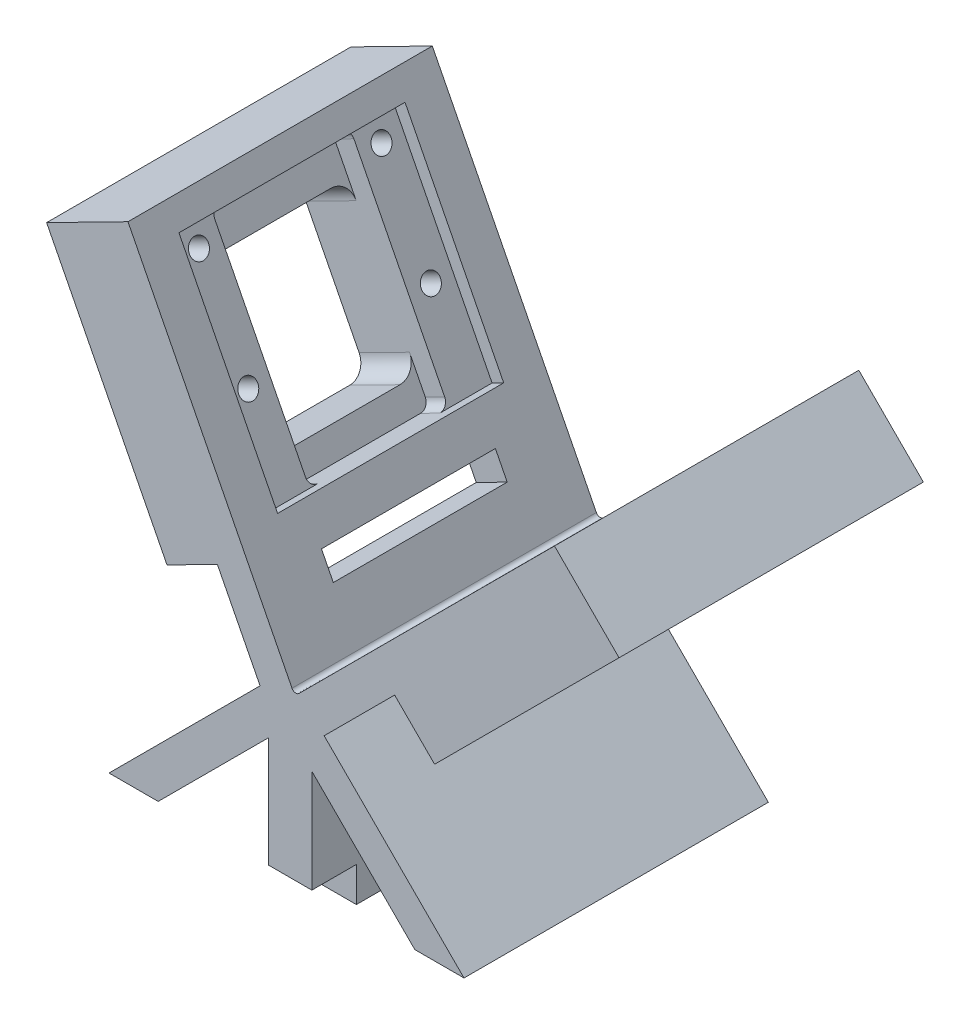
SolidWorks part; units mm, degrees
ref_plane "Front Plane" through (0, 0, 0) normal (0, 0, 1) x (1, 0, 0)
ref_plane "Top Plane" through (0, 0, 0) normal (0, 1, 0) x (1, 0, 0)
ref_plane "Right Plane" through (0, 0, 0) normal (1, 0, 0) x (0, 0, -1)
sketch "Sketch1" plane through (0, 0, 0) normal (0, 0, 1) x (1, 0, 0)
  line L0 (6.55, 4.55) -> (-6.55, 4.55)
  line L1 (4.05, 2.05) -> (-4.05, 2.05)
  line L2 (4.05, 2.05) -> (4.05, -2.05)
  line L3 (4.05, -2.05) -> (2.05, -2.05)
  line L4 (-4.05, 2.05) -> (-4.05, -2.05)
  line L5 (4.05, 2.05) -> (-4.05, -2.05) construction
  line L6 (4.05, -2.05) -> (-4.05, 2.05) construction
  line L7 (-6.55, 4.55) -> (-6.55, -4.55)
  line L8 (6.55, -4.55) -> (2.05, -4.55)
  line L9 (6.55, 4.55) -> (6.55, -4.55)
  line L10 (0, 0) -> (0, -4.55) construction
  line L11 (-2.05, -2.05) -> (-2.05, -4.55)
  line L12 (2.05, -2.05) -> (2.05, -4.55)
  line L13 (-2.05, -4.55) -> (-6.55, -4.55)
  line L14 (6.55, -4.55) -> (-6.55, -4.55) construction
  line L15 (-2.05, -2.05) -> (-4.05, -2.05)
  line L16 (4.05, -2.05) -> (-4.05, -2.05) construction
  line L17 (0, -2.05) -> (0, -4.55) construction
  point P0 (0, 0)
  dimension "D1" = 8.1
  dimension "D2" = 4.1
  dimension "D6" = 4.1
  dimension "D3" = 2.5
  dimension "D4" = 2.05
  dimension "D5" = 2.05
extrude "Boss-Extrude1" add sketch "Sketch1" along normal blind 35
sketch "Sketch2" plane through (0, 0, 35) normal (0, 0, 1) x (1, 0, 0)
  line L0 (0, 4.55) -> (0, 29.55) construction
  line L1 (6.55, 4.55) -> (-6.55, 4.55) construction
  line L2 (2.5, 4.55) -> (2.5, 25.7216)
  line L3 (-2.5, 4.55) -> (-2.5, 26.5511)
  line L4 (-2.5, 4.55) -> (2.5, 4.55)
  line L6 (0, 26.05) -> (31.8198, 57.8698) construction
  line L7 (0, 26.05) -> (-20.4296, 66.1453) construction
  line L8 (2.5, 25.7216) -> (33.234, 56.4556)
  line L9 (0.5323, 29.4107) -> (30.4056, 59.284)
  line L10 (1.4142, 24.6358) -> (33.234, 56.4556) construction
  line L11 (-2.5, 26.5511) -> (-22.2116, 65.2373)
  line L12 (-1.782, 25.142) -> (-22.2116, 65.2373) construction
  line L13 (-1.4142, 27.4642) -> (30.4056, 59.284) construction
  line L14 (0.5323, 29.4107) -> (-18.6476, 67.0533)
  line L15 (2.5, 4.55) -> (2.5, 29.55) construction
  line L17 (-2.5, 4.55) -> (-2.5, 29.55) construction
  line L18 (30.4056, 59.284) -> (33.234, 56.4556)
  line L19 (-22.2116, 65.2373) -> (-18.6476, 67.0533)
  dimension "D1" = 25
  dimension "D4" = 27
  dimension "D5" = 45
  dimension "D6" = 3.5
  dimension "D7" = 45
  dimension "D8" = 45
  dimension "D11" = 2
  dimension "D2" = 2.5
  dimension "D3" = 2.5
  dimension "D9" = 2
  dimension "D10" = 2
  dimension "D12" = 2
extrude "Boss-Extrude2" add sketch "Sketch2" against normal through all
fillet "Fillet1" radius 0.5 1 edges at (0.5323, 29.4107, 17.5)
sketch "Sketch3" plane through (-14.4392, 14.4392, 0) normal (-0.7071, 0.7071, 0) x (0, 0, 1)
  line L0 (0, 63.4201) -> (35, 63.4201) construction
  line L1 (4.5, 60.4201) -> (30.5, 60.4201)
  line L2 (4.5, 60.4201) -> (4.5, 35.4201)
  line L3 (4.5, 35.4201) -> (30.5, 35.4201)
  line L4 (30.5, 60.4201) -> (30.5, 35.4201)
  line L5 (4.5, 60.4201) -> (30.5, 35.4201) construction
  line L6 (4.5, 35.4201) -> (30.5, 60.4201) construction
  line L7 (17.5, 47.9201) -> (17.5, 63.4201) construction
  point P0 (17.5, 47.9201)
  dimension "D1" = 3
  dimension "D2" = 25
  dimension "D3" = 26
extrude "Cut-Extrude1" cut sketch "Sketch3" against normal blind 1.5
sketch "Sketch4" plane through (-13.3786, 13.3786, 0) normal (-0.7071, 0.7071, 0) x (0, 0, 1)
  line L2 (25.5, 35.4201) -> (25.5, 60.4201)
  line L3 (25.5, 35.4201) -> (25.5, 60.4201)
  line L4 (9.5, 60.4201) -> (25.5, 60.4201)
  line L5 (9.5, 60.4201) -> (9.5, 35.4201)
  line L6 (9.5, 60.4201) -> (9.5, 35.4201)
  line L7 (9.5, 35.4201) -> (26.4646, 35.4201)
  line M4 (30.5, 60.4201) -> (4.5, 60.4201)
  line M6 (4.5, 35.4201) -> (30.5, 35.4201)
  dimension "D1" = 5
  dimension "D2" = 5
extrude "Cut-Extrude2" cut sketch "Sketch4" against normal blind 5 contours L6 L3 M4 M6 region at (20.5061, 47.2632, 17.5)
fillet "Fillet3" radius 1 4 edges at (30.2288, 55.2182, 9.5) (30.2288, 55.2182, 25.5) (12.5511, 37.5405, 25.5) (12.5511, 37.5405, 9.5)
sketch "Sketch5" plane through (12.3195, 6.2771, 0) normal (0.891, 0.454, 0) x (0, 0, -1)
  line L0 (-17.5, 68.2107) -> (-17.5, 52.7107) construction
  line L1 (-30.5, 65.2107) -> (-4.5, 65.2107)
  line L2 (-30.5, 65.2107) -> (-30.5, 40.2107)
  line L3 (-30.5, 40.2107) -> (-4.5, 40.2107)
  line L4 (-4.5, 65.2107) -> (-4.5, 40.2107)
  line L5 (-30.5, 65.2107) -> (-4.5, 40.2107) construction
  line L6 (-30.5, 40.2107) -> (-4.5, 65.2107) construction
  line L7 (0, 68.2107) -> (-35, 68.2107) construction
  point P0 (-17.5, 52.7107)
  dimension "D1" = 3
  dimension "D2" = 25
  dimension "D3" = 26
extrude "Cut-Extrude3" cut sketch "Sketch5" against normal blind 1.5
sketch "Sketch6" plane through (10.9829, 5.5961, 0) normal (0.891, 0.454, 0) x (0, 0, -1)
  line L2 (-25.5, 65.2107) -> (-25.5, 40.2107)
  line L3 (-25.5, 65.2107) -> (-25.5, 40.2107)
  line L4 (-9.5, 65.2107) -> (-25.5, 65.2107)
  line L5 (-9.5, 40.2107) -> (-9.5, 65.2107)
  line L6 (-9.5, 40.2107) -> (-9.5, 65.2107)
  line L7 (-25.5, 40.2107) -> (-9.5, 40.2107)
  dimension "D1" = 5
  dimension "D2" = 5
extrude "Cut-Extrude4" cut sketch "Sketch6" against normal blind 5
fillet "Fillet4" radius 1 4 edges at (-8.3861, 40.8566, 9.5) (-19.7359, 63.1318, 9.5) (-19.7359, 63.1318, 25.5) (-8.3861, 40.8566, 25.5)
sketch "Sketch8" plane through (-11.6108, 11.6108, 0) normal (0.7071, -0.7071, 0) x (0, 0, -1)
  line L0 (-17.5, 29.4201) -> (-17.5, 35.4201) construction
  line L1 (-27.5, 30.9201) -> (-7.5, 30.9201)
  line L2 (-27.5, 30.9201) -> (-27.5, 27.9201)
  line L3 (-27.5, 27.9201) -> (-7.5, 27.9201)
  line L4 (-7.5, 30.9201) -> (-7.5, 27.9201)
  line L5 (-27.5, 30.9201) -> (-7.5, 27.9201) construction
  line L6 (-27.5, 27.9201) -> (-7.5, 30.9201) construction
  line L7 (-24.5, 35.4201) -> (-10.5, 35.4201) construction
  point P0 (-17.5, 29.4201)
  dimension "D1" = 3
  dimension "D2" = 6
  dimension "D3" = 20
extrude "Cut-Extrude5" cut sketch "Sketch8" against normal blind 4
sketch "Sketch9" plane through (8.7554, 4.4611, 0) normal (-0.891, -0.454, 0) x (0, 0, 1)
  line L0 (17.5, 40.2107) -> (17.5, 34.2107) construction
  line L2 (10.5, 40.2107) -> (24.5, 40.2107) construction
  line L3 (7.5, 35.7107) -> (27.5, 35.7107)
  line L4 (7.5, 35.7107) -> (7.5, 32.7107)
  line L5 (7.5, 32.7107) -> (27.5, 32.7107)
  line L6 (27.5, 35.7107) -> (27.5, 32.7107)
  line L7 (7.5, 35.7107) -> (27.5, 32.7107) construction
  line L8 (7.5, 32.7107) -> (27.5, 35.7107) construction
  dimension "D1" = 6
  dimension "D2" = 20
  dimension "D3" = 3
extrude "Cut-Extrude6" cut sketch "Sketch9" against normal blind 4
sketch "Sketch10" plane through (-2.5, 0, 0) normal (-1, 0, 0) x (0, 0, 1)
  line L2 (17.5, 4.55) -> (17.5, 19.55) construction
  line L3 (35, 4.55) -> (0, 4.55) construction
  line L4 (7.5, 21.05) -> (27.5, 21.05)
  line L5 (7.5, 21.05) -> (7.5, 18.05)
  line L6 (7.5, 18.05) -> (27.5, 18.05)
  line L7 (27.5, 21.05) -> (27.5, 18.05)
  line L8 (7.5, 21.05) -> (27.5, 18.05) construction
  line L9 (7.5, 18.05) -> (27.5, 21.05) construction
  point P6 (17.5, 19.55)
  dimension "D1" = 20
  dimension "D2" = 3
  dimension "D3" = 15
extrude "Cut-Extrude7" cut sketch "Sketch10" against normal blind 4
sketch "Sketch11" plane through (-13.3786, 13.3786, 0) normal (-0.7071, 0.7071, 0) x (0, 0, 1)
  line L0 (7, 45.4201) -> (7, 57.9201) construction
  line L1 (7, 57.9201) -> (28, 57.9201) construction
  line L2 (28, 57.9201) -> (28, 45.4201) construction
  line L3 (28, 45.4201) -> (7, 45.4201) construction
  line L4 (30.5, 60.4201) -> (4.5, 60.4201) construction
  line L5 (4.5, 60.4201) -> (4.5, 35.4201) construction
  circle A1 centre (28, 57.9201) radius 1.1
  circle A3 centre (7, 57.9201) radius 1.1
  circle A5 centre (28, 45.4201) radius 1.1
  circle A7 centre (7, 45.4201) radius 1.1
  dimension "D3" = 2.2
  dimension "D1" = 21
  dimension "D2" = 12.5
  dimension "D4" = 2.5
  dimension "D5" = 2.5
extrude "Cut-Extrude8" cut sketch "Sketch11" against normal blind 10
sketch "Sketch12" plane through (10.9829, 5.5961, 0) normal (0.891, 0.454, 0) x (0, 0, -1)
  line L0 (-28, 62.7107) -> (-28, 50.2107) construction
  line L2 (-28, 50.2107) -> (-7, 50.2107) construction
  line L5 (-7, 50.2107) -> (-7, 62.7107) construction
  line L6 (-7, 62.7107) -> (-28, 62.7107) construction
  line L7 (-4.5, 65.2107) -> (-30.5, 65.2107) construction
  line L8 (-30.5, 65.2107) -> (-30.5, 40.2107) construction
  circle A1 centre (-7, 62.7107) radius 1.1
  circle A3 centre (-28, 62.7107) radius 1.1
  circle A5 centre (-7, 50.2107) radius 1.1
  circle A7 centre (-28, 50.2107) radius 1.1
  dimension "D5" = 2.2
  dimension "D1" = 12.5
  dimension "D2" = 21
  dimension "D3" = 2.5
  dimension "D4" = 2.5
extrude "Cut-Extrude9" cut sketch "Sketch12" against normal blind 5
sketch "Sketch14" plane through (6.55, 0, 0) normal (1, 0, 0) x (0, 0, -1)
  line L0 (-35, -0.1) -> (0, 0) construction
  line L3 (-35, 1.8508) -> (0, 1.8508)
  line L4 (-35, 1.8508) -> (-35, -1.9508)
  line L5 (-35, -1.9508) -> (0, -1.9508)
  line L6 (0, 1.8508) -> (0, -1.9508)
  line L7 (-35, 1.8508) -> (0, -1.9508) construction
  line L8 (-35, -1.9508) -> (0, 1.8508) construction
  point P5 (-17.5, -0.05)
extrude "Boss-Extrude3" add sketch "Sketch14" along normal blind 3.5 and the other way blind 1
sketch "Sketch15" plane through (0, 1.8508, 0) normal (0, 1, 0) x (1, 0, 0)
  line L6 (6.55, -35) -> (6.55, 0) construction
  line L7 (6.55, -33) -> (6.55, -2)
  line L9 (8.05, -33) -> (6.55, -33)
  line L10 (6.55, -2) -> (8.05, -2)
  line L11 (8.05, -2) -> (8.05, -33)
  line L12 (8.05, -33) -> (6.55, -33)
  line L13 (6.55, -2) -> (8.05, -2)
  line L14 (8.05, -2) -> (8.05, -33)
  dimension "D1" = 2
extrude "Cut-Extrude10" cut sketch "Sketch15" against normal blind 5
sketch "Sketch16" plane through (0, 4.55, 0) normal (0, 1, 0) x (1, 0, 0)
  line L1 (-30.4197, 7.2021) -> (26.8386, 7.2021)
  line L2 (-30.4197, 7.2021) -> (-30.4197, -38.2329)
  line L3 (-30.4197, -38.2329) -> (26.8386, -38.2329)
  line L4 (26.8386, 7.2021) -> (26.8386, -38.2329)
  line L5 (-30.4197, 7.2021) -> (26.8386, -38.2329) construction
  line L6 (-30.4197, -38.2329) -> (26.8386, 7.2021) construction
  point P0 (-1.7905, -15.5154)
extrude "Cut-Extrude11" [suppressed] cut sketch "Sketch16" against normal blind 10 and the other way blind 1
sketch "Sketch18" plane through (-11.6108, 11.6108, 0) normal (0.7071, -0.7071, 0) x (0, 0, -1)
  line L0 (-35, 19.9557) -> (-35, 63.4201) construction
  line L1 (0, 19.9557) -> (0, 63.4201) construction
  line L2 (0, 63.4201) -> (-35, 63.4201) construction
  line L3 (-35, 33.4201) -> (-35, 63.4201)
  line L4 (0, 33.4201) -> (0, 63.4201)
  line L5 (0, 63.4201) -> (-35, 63.4201)
  line L6 (-25.5, 59.4201) -> (-25.5, 36.4201) construction
  line L7 (-9.5, 36.4201) -> (-9.5, 59.4201) construction
  line L9 (-25.5, 58.9201) -> (-25.5, 38.9201)
  line L10 (-9.5, 38.9201) -> (-9.5, 58.9201)
  line L11 (-35, 33.4201) -> (0, 33.4201)
  line L12 (-25.5, 58.9201) -> (-9.5, 58.9201)
  line L13 (-25.5, 38.9201) -> (-9.5, 38.9201)
  line L14 (-24.5, 35.4201) -> (-10.5, 35.4201) construction
  circle A4 centre (-7, 57.9201) radius 1.1 construction
  circle A5 centre (-7, 45.4201) radius 1.1 construction
  circle A6 centre (-28, 45.4201) radius 1.1 construction
  circle A7 centre (-28, 57.9201) radius 1.1 construction
  circle A8 centre (-7, 57.9201) radius 1.1
  circle A9 centre (-7, 45.4201) radius 1.1
  circle A10 centre (-28, 45.4201) radius 1.1
  circle A11 centre (-28, 57.9201) radius 1.1
  dimension "D1" = 2
  dimension "D2" = 4.5
  dimension "D3" = 3.5
extrude "Boss-Extrude4" add sketch "Sketch18" along normal blind 6.5
sketch "Sketch19" plane through (8.7554, 4.4611, 0) normal (-0.891, -0.454, 0) x (0, 0, 1)
  line L0 (25.5, 41.2107) -> (25.5, 64.2107) construction
  line L1 (9.5, 64.2107) -> (9.5, 41.2107) construction
  line L2 (25.5, 43.2107) -> (25.5, 60.7107)
  line L3 (9.5, 60.7107) -> (9.5, 43.2107)
  line L4 (35, 68.2107) -> (0, 68.2107)
  line L5 (0, 68.2107) -> (0, 24.7922)
  line L6 (0, 24.7922) -> (35, 24.7922)
  line L7 (35, 24.7922) -> (35, 68.2107)
  line L8 (35, 68.2107) -> (0, 68.2107)
  line L9 (0, 68.2107) -> (0, 37.7107)
  line L11 (35, 37.7107) -> (35, 68.2107)
  line L12 (9.5, 60.7107) -> (25.5, 60.7107)
  line L13 (9.5, 43.2107) -> (25.5, 43.2107)
  line L14 (24.5, 65.2107) -> (10.5, 65.2107) construction
  line L15 (10.5, 40.2107) -> (24.5, 40.2107) construction
  line L16 (0, 37.7107) -> (35, 37.7107)
  circle A0 centre (28, 62.7107) radius 1.1 construction
  circle A1 centre (28, 50.2107) radius 1.1 construction
  circle A6 centre (7, 50.2107) radius 1.1 construction
  circle A7 centre (7, 62.7107) radius 1.1 construction
  circle A8 centre (28, 50.2107) radius 1.1
  circle A9 centre (7, 50.2107) radius 1.1
  circle A10 centre (7, 62.7107) radius 1.1
  circle A11 centre (28, 62.7107) radius 1.1
  dimension "D2" = 4.5
  dimension "D3" = 3
  dimension "D4" = 2.5
  dimension "D1" = 0
extrude "Boss-Extrude5" add sketch "Sketch19" along normal blind 6.5
sketch "Sketch20" plane through (0, 4.55, 0) normal (0, 1, 0) x (1, 0, 0)
  line L1 (-46.7008, 10.2311) -> (46.7008, 10.2311)
  line L2 (-46.7008, 10.2311) -> (-46.7008, -43.0242)
  line L3 (-46.7008, -43.0242) -> (46.7008, -43.0242)
  line L4 (46.7008, 10.2311) -> (46.7008, -43.0242)
  line L5 (-46.7008, 10.2311) -> (46.7008, -43.0242) construction
  line L6 (-46.7008, -43.0242) -> (46.7008, 10.2311) construction
  point P0 (0, -16.3965)
extrude "Cut-Extrude12" cut sketch "Sketch20" against normal blind 10 and the other way blind 2.5
sketch "Sketch21" plane through (0, 0, 35) normal (0, 0, 1) x (1, 0, 0)
  line L0 (2.5, 7.05) -> (2.5, 25.7216) construction
  line L1 (-2.5, 7.05) -> (2.5, 7.05)
  line L2 (-2.5, 7.05) -> (-2.5, 11.05)
  line L3 (-2.5, 11.05) -> (2.5, 11.05)
  line L4 (2.5, 7.05) -> (2.5, 11.05)
  dimension "D1" = 4
extrude "Cut-Extrude13" cut sketch "Sketch21" against normal blind 5.125
ref_plane "Plane1" through (0, 0, 17.5) normal (0, 0, -1) x (-1, 0, 0)
mirror "Mirror1" about plane through (0, 0, 17.5) normal (0, 0, -1) of "Cut-Extrude13"
fillet "Fillet9" radius 2 4 edges at (-21.7024, 57.0793, 25.5) (-13.7576, 41.4867, 9.5) (-13.7576, 41.4867, 25.5) (-21.7024, 57.0793, 9.5)
fillet "Fillet10" radius 2 4 edges at (32.3501, 50.9755, 9.5) (32.3501, 50.9755, 25.5) (18.208, 36.8334, 25.5) (18.208, 36.8334, 9.5)
sketch "Sketch25" plane through (0, 0, 35) normal (0, 0, 1) x (1, 0, 0)
  line L0 (2.5, 25.7216) -> (17.1716, 11.05) construction
  line L1 (-2.5, 26.5511) -> (-18.0011, 11.05) construction
  line L2 (1.0858, 24.3074) -> (19.7574, 5.6358) construction
  line L5 (0, 11.05) -> (0, 68.5669) construction
  line L6 (1.0858, 24.3074) -> (14.3431, 11.05)
  line L7 (3.0938, 27.9562) -> (20, 11.05)
  line L8 (-2.5946, 29.285) -> (-20.8296, 11.05)
  line L9 (-1.0858, 25.1369) -> (-15.1727, 11.05)
  line L10 (3.9142, 27.1358) -> (22.5858, 8.4642) construction
  line L11 (-3.9142, 27.9654) -> (-23.4154, 8.4642) construction
  line L12 (-2.5946, 29.285) -> (-1.0858, 25.1369)
  line L13 (3.0938, 27.9562) -> (1.0858, 24.3074)
  line L14 (-1.0858, 25.1369) -> (-20.5869, 5.6358) construction
  line L18 (-20.8296, 11.05) -> (-15.1727, 11.05)
  line L19 (2.5, 25.7216) -> (21.1716, 7.05) construction
  line L20 (-2.5, 26.5511) -> (-22.0011, 7.05) construction
  line L21 (14.3431, 11.05) -> (20, 11.05)
  dimension "D3" = 2
  dimension "D4" = 2
  dimension "D5" = 2
  dimension "D6" = 2
extrude "Boss-Extrude8" add sketch "Sketch25" against normal through all
